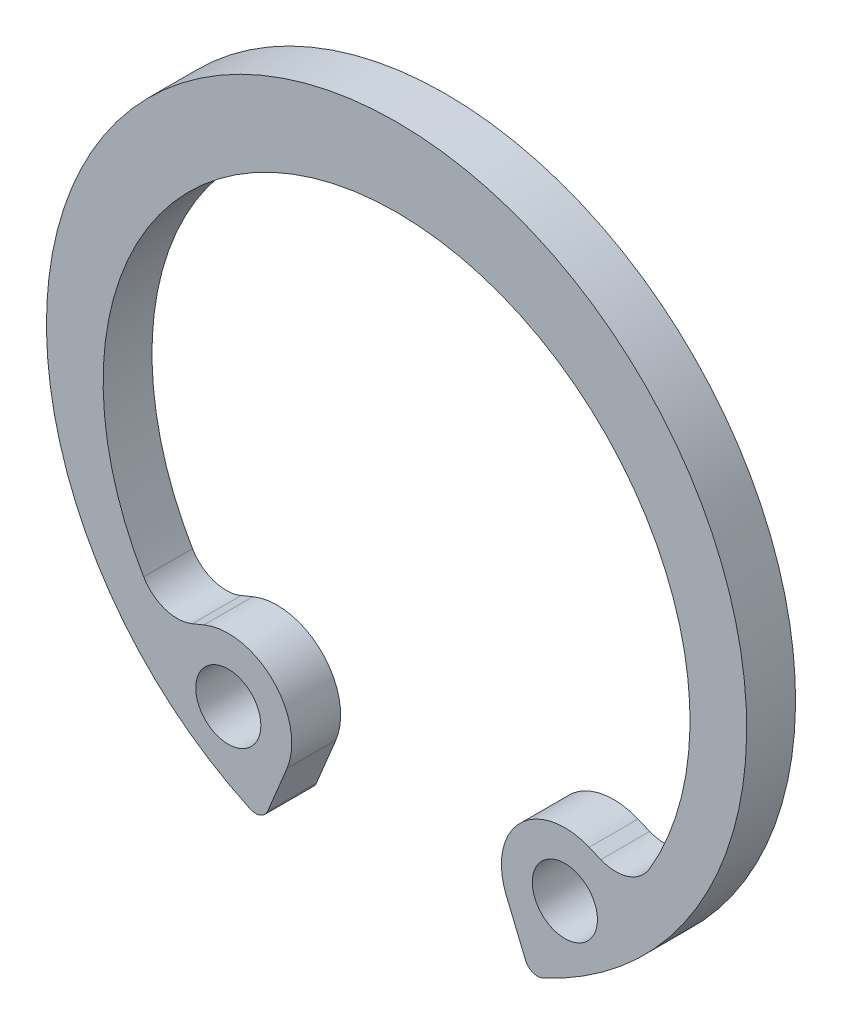
SolidWorks part; units mm, degrees
ref_plane "Front Plane" through (0, 0, 0) normal (0, 0, 1) x (1, 0, 0)
ref_plane "Top Plane" through (0, 0, 0) normal (0, 1, 0) x (1, 0, 0)
ref_plane "Right Plane" through (0, 0, 0) normal (1, 0, 0) x (0, 0, -1)
sketch "BodySke" plane through (0, 0, 0) normal (0, 0, 1) x (1, 0, 0)
  line L0 (0, -7.6074) -> (0, 7.215) construction
  line L1 (3.3663, -8.127) -> (4.1138, -9.9317)
  line L2 (-3.3663, -8.127) -> (-4.1138, -9.9317)
  line L3 (4.1138, -9.9317) -> (5.9992, -9.9317) construction
  line L4 (5.9132, -5.5801) -> (7.179, -6.1044)
  line L5 (-5.9132, -5.5801) -> (-7.179, -6.1044)
  arc A0 (4.1138, -9.9317) -> (-4.1138, -9.9317) centre (0, 0) ccw
  arc A1 (0, -9.67) -> (6.889, -6.467) centre (0, -0.66) ccw construction
  circle A2 centre (5.1673, -7.381) radius 1
  circle A3 centre (0, 0) radius 9.01 construction
  circle A4 centre (-5.1673, -7.381) radius 1
  arc A5 (-7.179, -6.1044) -> (7.179, -6.1044) centre (0, -0.66) cw
  arc A6 (6.889, -6.467) -> (6.6338, -6.0969) centre (5.1673, -7.381) ccw construction
  arc A8 (5.9132, -5.5801) -> (3.3663, -8.127) centre (5.1673, -7.381) ccw
  arc A9 (7.179, -6.1044) -> (-7.179, -6.1044) centre (0, -0.66) ccw
  arc A10 (-5.9132, -5.5801) -> (-3.3663, -8.127) centre (-5.1673, -7.381) cw
  dimension "D3" = 18.02
  dimension "Hole_dia" = 2
  dimension "Groove_length" = 4.5
  dimension "D2" = 22.5
  dimension "D1" = 45
extrude "BaseBody" add sketch "BodySke" along normal blind 1.5 contours A1 L1 A0 | A1 | A1 | A9 L2 A4 region at (3.9998, -6.2136, 0)
fillet "Fillet1" radius 1.2 2 edges at (7.179, -6.1044, 0.75) (-7.179, -6.1044, 0.75)
fillet "Fillet2" radius 0.4 2 edges at (4.1138, -9.9317, 0.75) (-4.1138, -9.9317, 0.75)
equation "\"D3@BodySke\" = \"Groove_Diameter@BodySke\" - 1.45 * \"Groove_depth@BodySke\""
equation "\"D1@Fillet1\" = \"Hole_dia@BodySke\" * 0.6"
equation "\"D1@Fillet2\" = \"Hole_dia@BodySke\" * 0.2"
